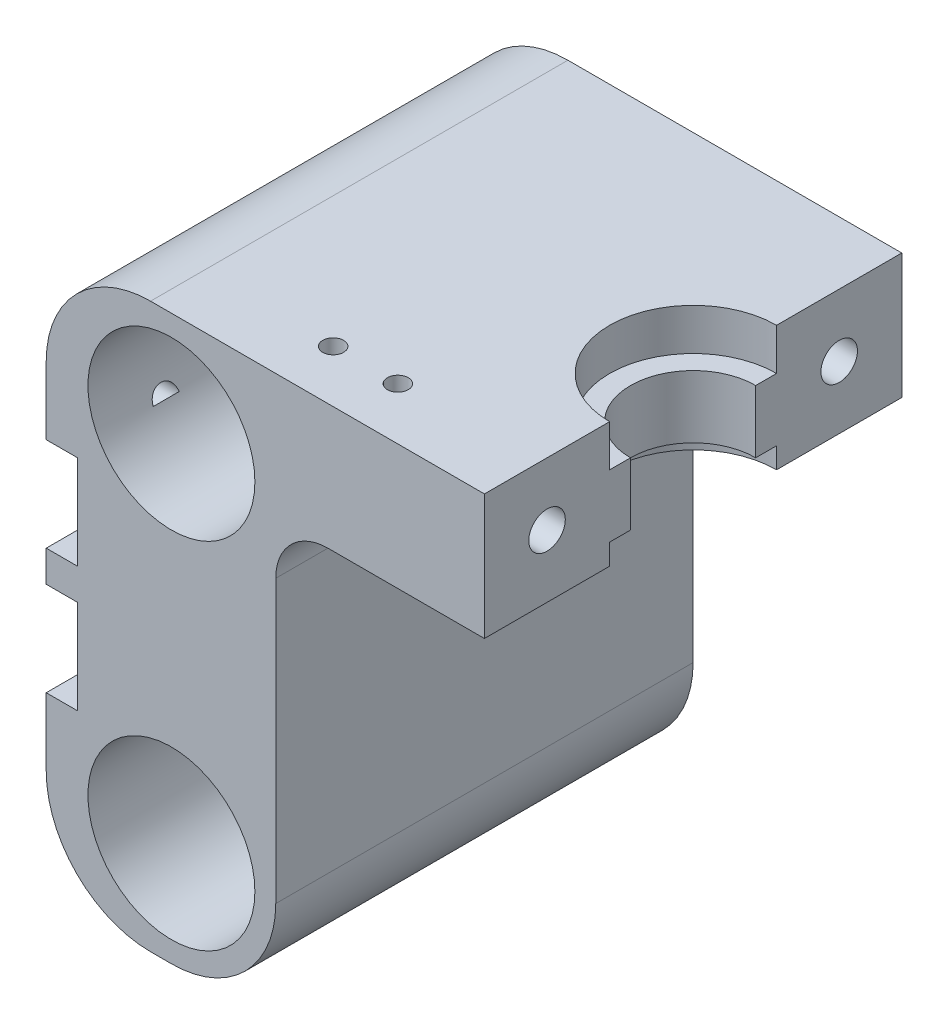
SolidWorks part; units mm, degrees
material "PLA"
ref_plane "Front Plane" through (0, 0, 0) normal (0, 0, 1) x (1, 0, 0)
ref_plane "Top Plane" through (0, 0, 0) normal (0, 1, 0) x (1, 0, 0)
ref_plane "Right Plane" through (0, 0, 0) normal (1, 0, 0) x (0, 0, -1)
sketch "Sketch1" plane through (0, 0, 0) normal (0, 0, 1) x (1, 0, 0)
  line L1 (0, 0) -> (22, 0)
  line L2 (0, 0) -> (0, 54)
  line L3 (0, 54) -> (22, 54)
  line L4 (22, 0) -> (22, 54)
  circle A0 centre (12, 10) radius 8
  circle A1 centre (12, 44) radius 8
  dimension "D3" = 16
  dimension "D1" = 22
  dimension "D2" = 34
  dimension "D4" = 10
  dimension "D5" = 10
  dimension "D7" = 12
extrude "Boss-Extrude1" add sketch "Sketch1" along normal blind 40
sketch "Sketch2" plane through (0, 0, 0) normal (-1, 0, 0) x (0, 0, 1)
  line L1 (0, 16.5) -> (48, 16.5)
  line L2 (0, 16.5) -> (0, 37.5)
  line L3 (0, 37.5) -> (48, 37.5)
  line L4 (48, 16.5) -> (48, 37.5)
  line L7 (40, 0) -> (0, 0) construction
  dimension "D1" = 21
  dimension "D2" = 16.5
extrude "Cut-Extrude1" cut sketch "Sketch2" against normal blind 3
sketch "Sketch6" plane through (22, 0, 0) normal (1, 0, 0) x (0, 0, -1)
  line L0 (0, 0) -> (0, 54) construction
  line L1 (-40, 54) -> (0, 54)
  line L2 (-40, 54) -> (-40, 42)
  line L3 (-40, 42) -> (0, 42)
  line L4 (0, 54) -> (0, 42)
  dimension "D1" = 12
extrude "Boss-Extrude2" add sketch "Sketch6" along normal blind 20
sketch "Sketch7" plane through (0, 54, 0) normal (0, 1, 0) x (1, 0, 0)
  line L0 (42, 0) -> (42, -40) construction
  circle A0 centre (42, -20) radius 8
  dimension "D1" = 16
extrude "Cut-Extrude5" cut sketch "Sketch7" against normal blind 4
extrude "Cut-Extrude6" cut sketch "Sketch7<2>" against normal blind 3 from offset 10 offset against normal yes
sketch "Sketch7<2>" plane through (0, 54, 0) normal (0, 1, 0) x (1, 0, 0) same geometry as "Sketch7"
sketch "Sketch8" plane through (0, 50, 0) normal (0, 1, 0) x (1, 0, 0)
  line L0 (42, -12) -> (42, -28) construction
  circle A0 centre (42, -20) radius 6
  dimension "D1" = 12
extrude "Cut-Extrude7" cut sketch "Sketch8" against normal blind 7
sketch "Sketch9" plane through (42, 0, 0) normal (1, 0, 0) x (0, 0, -1)
  line L0 (-26, 50) -> (-26, 44) construction
  line L1 (-14, 44) -> (-14, 50) construction
  line L2 (0, 54) -> (-12, 54) construction
  line L3 (-28, 54) -> (-40, 54) construction
  circle A0 centre (-34, 48) radius 1.75
  circle A1 centre (-6, 48) radius 1.75
  dimension "D1" = 3.5
  dimension "D2" = 8
  dimension "D3" = 8
  dimension "D4" = 6
  dimension "D5" = 6
extrude "Cut-Extrude8" cut sketch "Sketch9" against normal blind 15
sketch "Sketch10" plane through (0, 0, 0) normal (-1, 0, 0) x (0, 0, 1)
  line L0 (40, 54) -> (40, 37.5) construction
  line L1 (40, 54) -> (0, 54) construction
  line L2 (0, 54) -> (0, 37.5) construction
  line L3 (33.5, 51) -> (33.5, 3) construction
  line L4 (40, 0) -> (0, 0) construction
  line L5 (6.5, 51) -> (6.5, 3) construction
  circle A0 centre (33.5, 51) radius 1.25 construction
  circle A1 centre (6.5, 51) radius 1.25 construction
  circle A2 centre (33.5, 3) radius 1.25 construction
  circle A3 centre (6.5, 3) radius 1.25 construction
  circle A6 centre (33.5, 40) radius 1.25
  circle A7 centre (33.5, 14) radius 1.25
  circle A8 centre (6.5, 14) radius 1.25
  circle A9 centre (6.5, 40) radius 1.25
  circle A10 centre (15, 40) radius 1.25
  circle A11 centre (25, 40) radius 1.25
  circle A12 centre (15, 14) radius 1.25
  circle A13 centre (25, 14) radius 1.25
  dimension "D2" = 3
  dimension "D6" = 2.5
  dimension "D7" = 11
  dimension "D1" = 6.5
  dimension "D3" = 6.5
  dimension "D4" = 3
  dimension "D5" = 11
extrude "Cut-Extrude9" cut sketch "Sketch10" against normal blind 5
sketch "Sketch13" plane through (0, 0, 0) normal (-1, 0, 0) x (0, 0, 1)
  line L0 (6.5, 40) -> (6.5, 14) construction
  line L1 (6.5, 14) -> (33.5, 14) construction
  line L2 (33.5, 14) -> (33.5, 40) construction
  circle A0 centre (6.5, 27) radius 1.25
  circle A1 centre (33.5, 27) radius 1.25
  dimension "D1" = 2.5
extrude "Cut-Extrude10" cut sketch "Sketch13" against normal blind 10
sketch "Sketch14" plane through (3, 0, 0) normal (-1, 0, 0) x (0, 0, 1)
  line L0 (0, 37.5) -> (0, 16.5) construction
  line L1 (0, 28.5) -> (40, 28.5)
  line L2 (0, 28.5) -> (0, 25.5)
  line L3 (0, 25.5) -> (40, 25.5)
  line L4 (40, 28.5) -> (40, 25.5)
  line L5 (40, 37.5) -> (40, 16.5) construction
  circle A0 centre (6.5, 27) radius 1.25 construction
  circle A1 centre (6.5, 27) radius 1.25
  circle A2 centre (33.5, 27) radius 1.25
  dimension "D1" = 3
  dimension "D2" = 1.5
extrude "Boss-Extrude3" add sketch "Sketch14" along normal up to surface (3 mm away) up to face at (0, 40, 26.25)
fillet "Fillet1" radius 10 3 edges at (0, 0, 20) (0, 54, 20) (22, 0, 20)
fillet "Fillet2" radius 5 1 edges at (22, 42, 20)
sketch "Sketch15" plane through (0, 54, 0) normal (0, 1, 0) x (1, 0, 0)
  circle A0 centre (22.5, -35) radius 1
  circle A1 centre (28.7, -35) radius 1
  dimension "D1" = 2
extrude "Cut-Extrude11" cut sketch "Sketch15" against normal blind 10
